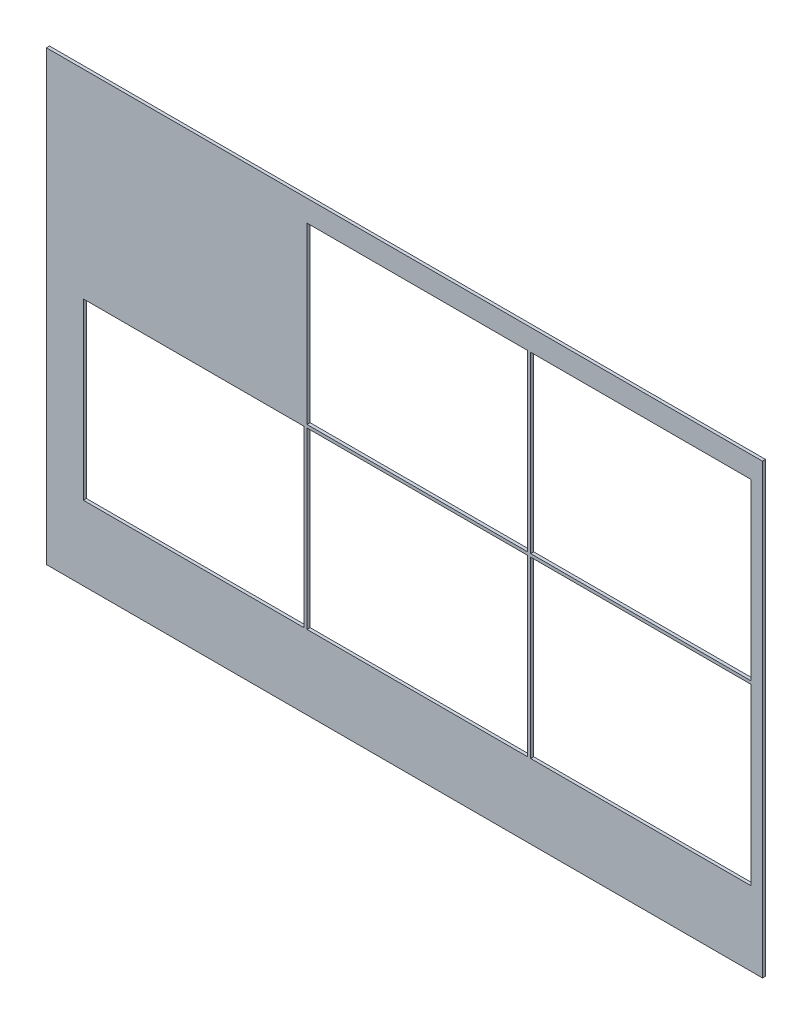
SolidWorks part; units mm, degrees
ref_plane "Спереди" through (0, 0, 0) normal (0, 0, 1) x (1, 0, 0)
ref_plane "Сверху" through (0, 0, 0) normal (0, 1, 0) x (1, 0, 0)
ref_plane "Справа" through (0, 0, 0) normal (1, 0, 0) x (0, 0, -1)
sketch "Эскиз1" plane through (0, 0, 0) normal (0, 0, 1) x (1, 0, 0)
  line L1 (447, 436.3) -> (447, -436.3) construction
  line L2 (447, -436.3) -> (-949, -436.3)
  line L3 (447, -436.3) -> (447, 436.3)
  line L4 (447, 436.3) -> (-949, 436.3)
  line L5 (-949, -436.3) -> (-949, 436.3)
  line L6 (441, -436.3) -> (447, -436.3) construction
extrude "Бобышка-Вытянуть1" add sketch "Эскиз1" against normal blind 6
sketch "Эскиз2" plane through (0, 0, 0) normal (0, 0, 1) x (1, 0, 0)
  line L1 (-441, 394.3) -> (-11, 394.3)
  line L2 (-441, 394.3) -> (-441, 54.3)
  line L3 (-441, 54.3) -> (-11, 54.3)
  line L4 (-11, 394.3) -> (-11, 54.3)
  dimension "D1" = 430
  dimension "D2" = 340
extrude "Вырез-Вытянуть1" cut sketch "Эскиз2" against normal through all
pattern_linear "Линейный массив1" count 2 spacing 436 along (1, 0, 0) count 2 spacing 346 along (0, -1, 0) of "Вырез-Вытянуть1"
sketch "Эскиз3" plane through (0, 0, 0) normal (0, 0, 1) x (1, 0, 0)
  line L1 (-447, -291.7) -> (-877, -291.7)
  line L2 (-447, -291.7) -> (-447, 48.3)
  line L3 (-447, 48.3) -> (-877, 48.3)
  line L4 (-877, -291.7) -> (-877, 48.3)
  line L5 (-441, 48.3) -> (-441, -291.7) construction
  line L6 (-11, 48.3) -> (-441, 48.3) construction
  dimension "D1" = 430
  dimension "D2" = 340
  dimension "D3" = 6
extrude "Вырез-Вытянуть2" cut sketch "Эскиз3" against normal through all
equation "\"Ширина груза\"= 420"
equation "\"Глубина груза\"= 490"
equation "\"Высота груза\"= 297"
equation "\"Ширина ячейки\"= \"Ширина груза\" + 10"
equation "\"Глубина ячейки\"= \"Глубина груза\" + 10"
equation "\"Высота ячейки\"= \"Высота груза\" + 10 + 13"
equation "\"Колво ячеек ширина\"= 2"
equation "\"Колво ячеек высота\"= 2"
equation "\"Толщина стенки\" = 6"
equation "\"Крепление дверцы\"= 5"
equation "\"Ширина рейки\"= \"Толщина шестерни\""
equation "\"Высота рейки\"= 20"
equation "\"Высота пола\"= 20"
equation "\"Колво полозьев\"= 5"
equation "\"Отступ рейки\"= 20"
equation "\"Глубина каретки\"= \"Глубина ячейки\" + 30 + \"Мотор Y высота корпуса\" + 20"
equation "\"Длинна рейки\"= ( \"Ширина ячейки\" + \"Толщина стенки\" + \"Крепление дверцы\" ) * \"Колво ячеек ширина\" + \"Ширина ячейки выгрузки\" * \"Колво выгрузки\" + \"Толщина стенки\""
equation "\"Отступ шпильки\"= 26"
equation "\"Диаметр шпильки\"= 5"
equation "\"Длинна шпильки\"= ( \"Высота ячейки\" + \"Толщина стенки\" + \"Высота пола\" ) * \"Колво ячеек высота\" + ( \"Толщина стенки\" + \"Отступ рейки\" ) * 2 "
equation "\"Ширина пластины\"= 50  "
equation "\"Высота зона выгрузки\"= \"Высота ячейки\" * 2 + \"Толщина стенки\" * 2"
equation "\"Колво выгрузки\"= 1"
equation "\"Ширина ячейки выгрузки\"= \"Ширина ячейки\" + \"Толщина стенки\" + \"Отступ крепления мотора фиксации\"*2"
equation "\"Отступ крепления мотора фиксации\" = 30"
equation "\"Мотор X ширина корпуса\"= 42.3"
equation "\"Мотор X высота корпуса\"= 42.3"
equation "\"Мотор X длина корпуса\"= 40"
equation "\"Мотор X вылет вала\"= 19.8"
equation "\"Мотор Y ширина корпуса\"= 42.3"
equation "\"Мотор Y высота корпуса\"= 42.3"
equation "\"Мотор Y длина корпуса\"= 48"
equation "\"Мотор Y вылет вала\"= 30"
equation "\"Мотор Z ширина корпуса\"= 42"
equation "\"Мотор Z высота корпуса\"= 42"
equation "\"Мотор Z длина корпуса\"= 40"
equation "\"Мотор Z вылет вала\"= 23"
equation "\"Мотор диаметр вала ПРЕДВ\"= 5"
equation "\"Мотор шаг крепления ПРЕДВ\"= 31"
equation "\"Мотор диаметр отверстий ПРЕДВ\"= 3"
equation "\"Мотор глубина отверстий ПРЕДВ\"= 4.5"
equation "\"Мотор диаметр буртика ПРЕДВ\"= 22"
equation "\"Мотор высота буртика ПРЕДВ\"= 2"
equation "\"Мотор диаметр шкива ПРЕДВ\"= 16"
equation "\"Мотор длина шкива ПРЕДВ\"= 12"
equation "\"Мотор отступ шкива ПРЕДВ\"= 5"
equation "\"Мотор X шаг градусов\"= 1.8"
equation "\"Мотор Y шаг градусов\"= 1.8"
equation "\"Мотор Z шаг градусов\"= 1.8"
equation "\"Мотор Y диаметр ротора\"= 25.78"
equation "\"Толщина шестерни\"= 10"
equation "\"D1@Бобышка-Вытянуть1\"=\"Толщина стенки\""
equation "\"D1@Эскиз2\"=\"Ширина ячейки\""
equation "\"D2@Эскиз2\"=\"Высота ячейки\" + \"Высота пола\""
equation "\"D3@Линейный массив1\"=\"Ширина ячейки\" + \"Толщина стенки\""
equation "\"D4@Линейный массив1\"=\"Высота ячейки\" + \"Высота пола\" + \"Толщина стенки\""
equation "\"D1@Эскиз3\"=\"Ширина ячейки\""
equation "\"D2@Эскиз3\"=\"Высота ячейки\" + \"Высота пола\""
equation "\"D3@Эскиз3\"=\"Толщина стенки\""
